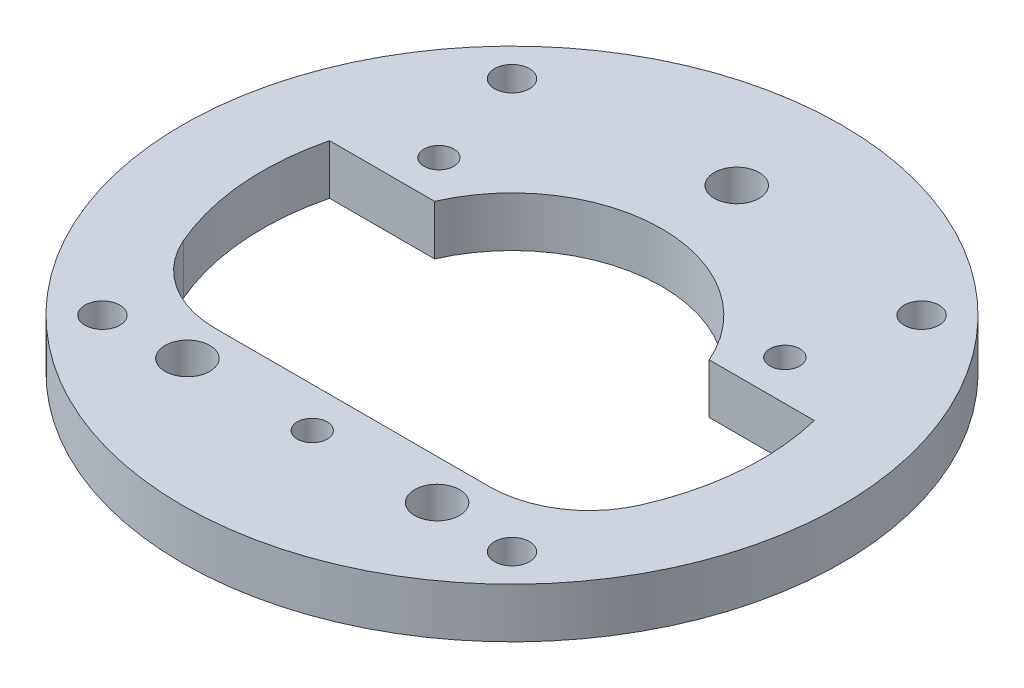
SolidWorks part; units mm, degrees
ref_plane "Front Plane" through (0, 0, 0) normal (0, 0, 1) x (1, 0, 0)
ref_plane "Top Plane" through (0, 0, 0) normal (0, 1, 0) x (1, 0, 0)
ref_plane "Right Plane" through (0, 0, 0) normal (1, 0, 0) x (0, 0, -1)
sketch "Sketch1" plane through (0, 0, 0) normal (0, 1, 0) x (1, 0, 0)
  circle A0 centre (0, 0) radius 33
  circle A1 centre (0, 0) radius 25
  dimension "D1" = 66
  dimension "D2" = 8
extrude "Boss-Extrude1" add sketch "Sketch1" along normal blind 5
sketch "Sketch2" plane through (0, 5, 0) normal (0, 1, 0) x (1, 0, 0)
  line L0 (-19.2094, -16) -> (19.2094, -16)
  line L1 (-24.2693, 6) -> (-13.7477, 6)
  line L2 (0, 0) -> (7.7557, 0) construction
  line L3 (13.7477, 6) -> (24.2693, 6)
  line L4 (-20.5061, 20.5061) -> (0, 0) construction
  circle A0 centre (0, 22.5) radius 2.25 construction
  circle A1 centre (-12.5, -20) radius 2.25 construction
  circle A2 centre (12.5, -20) radius 2.25 construction
  circle A3 centre (0, -20) radius 1.5 construction
  circle A4 centre (0, 0) radius 20 construction
  circle A5 centre (-17.3205, 10) radius 1.5 construction
  circle A6 centre (0, 0) radius 25 construction
  circle A7 centre (17.3205, 10) radius 1.5 construction
  arc A8 (-13.7477, 6) -> (13.7477, 6) centre (0, 0) cw
  arc A9 (24.2693, 6) -> (-24.2882, 5.9232) centre (0, 0) ccw
  arc A10 (19.2094, -16) -> (-19.2094, -16) centre (0, 0) cw
  circle A12 centre (0, 0) radius 29 construction
  circle A13 centre (0, 0) radius 33 construction
  circle A14 centre (-20.5061, 20.5061) radius 1.75 construction
  circle A15 centre (20.5061, 20.5061) radius 1.75 construction
  circle A16 centre (20.5061, -20.5061) radius 1.75 construction
  circle A17 centre (-20.5061, -20.5061) radius 1.75 construction
  point P19 (0, 0)
  point P25 (0, 0)
  point P26 (0, 0)
  point P27 (0, 0)
  point P28 (0, 0)
  point P29 (0, 0)
  point P35 (0, 0)
  point P36 (-17.3205, 10.253)
  point P44 (0, 0)
  circle M2 centre (0, 0) radius 25
  dimension "D5" = 4.5
  dimension "D6" = 4.5
  dimension "D7" = 4.5
  dimension "D10" = 3
  dimension "D12" = 15
  dimension "D16" = 3.5
  dimension "D1" = 25
  dimension "D2" = 12.5
  dimension "D3" = 22.5
  dimension "D4" = 20
  dimension "D9" = 5
  dimension "D11" = 4
  dimension "D13" = 4
  dimension "D14" = 4
  dimension "D15" = 135
  dimension "D18" = 5
  dimension "D8" = 3
  dimension "D17" = 4
extrude "Saliente-Extruir1" add sketch "Sketch2" against normal up to surface (5 mm away) contours L1 A8 L3 M2 | L0 M2 region at (0, 5, 19.6621) region at (0, 5, -15.401) up to face at (0, 0, 33)
sketch "Croquis1" plane through (0, 5, 0) normal (0, 1, 0) x (1, 0, 0)
  circle A0 centre (-20.5061, 20.5061) radius 1.75 construction
  circle A1 centre (-20.5061, 20.5061) radius 1.75
  circle A2 centre (0, 22.5) radius 2.25 construction
  circle A3 centre (0, 22.5) radius 2.25
  circle A4 centre (20.5061, 20.5061) radius 1.75 construction
  circle A5 centre (20.5061, 20.5061) radius 1.75
  circle A6 centre (-17.3205, 10) radius 1.5 construction
  circle A7 centre (-17.3205, 10) radius 1.5
  circle A8 centre (17.3205, 10) radius 1.5 construction
  circle A9 centre (17.3205, 10) radius 1.5
  circle A10 centre (0, -20) radius 1.5 construction
  circle A11 centre (0, -20) radius 1.5
  circle A12 centre (12.5, -20) radius 2.25 construction
  circle A13 centre (12.5, -20) radius 2.25
  circle A14 centre (-12.5, -20) radius 2.25 construction
  circle A15 centre (-12.5, -20) radius 2.25
  circle A16 centre (-20.5061, -20.5061) radius 1.75 construction
  circle A17 centre (-20.5061, -20.5061) radius 1.75
  circle A18 centre (20.5061, -20.5061) radius 1.75 construction
  circle A19 centre (20.5061, -20.5061) radius 1.75
extrude "Cortar-Extruir1" cut sketch "Croquis1" against normal up to next
fillet "Redondeo1" radius 10 2 edges at (19.2094, 2.5, 16) (-19.2094, 2.5, 16)
equation "\"D2@Sketch2\"=\"D1@Sketch2\"/2"
equation "\"D6@Sketch2\"=\"D5@Sketch2\""
equation "\"D7@Sketch2\"=\"D6@Sketch2\""
equation "\"D10@Sketch2\"=\"D8@Sketch2\""
